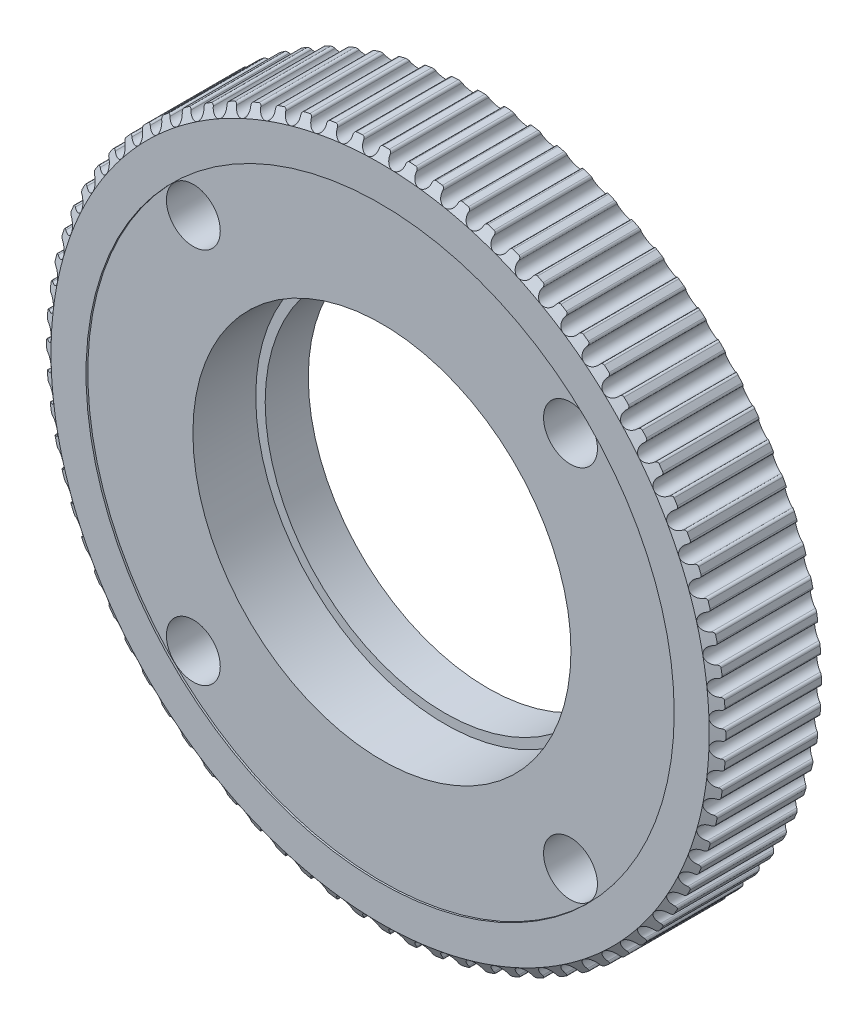
SolidWorks part; units mm, degrees
ref_plane "Front Plane" through (0, 0, 0) normal (0, 0, 1) x (1, 0, 0)
ref_plane "Top Plane" through (0, 0, 0) normal (0, 1, 0) x (1, 0, 0)
ref_plane "Right Plane" through (0, 0, 0) normal (1, 0, 0) x (0, 0, -1)
sketch "Sketch1" plane through (0, 0, 0) normal (0, 0, 1) x (1, 0, 0)
  circle A0 centre (0, 0) radius 37.8162
  circle A1 centre (0, 0) radius 38.1972 construction
  dimension "D1" = 76.3944
  dimension "D2" = 0.381
extrude "Boss-Extrude1" add sketch "Sketch1" along normal mid plane 12
sketch "Sketch2" plane through (0, 0, 6) normal (0, 0, 1) x (1, 0, 0)
  line L0 (0, 0) -> (0, 37.8162) construction
  line L1 (0, 0) -> (1.4847, 37.787) construction
  line L2 (0, 0) -> (-1.4847, 37.787) construction
  line L3 (-1.4387, 36.6179) -> (-1.5286, 38.9064)
  line L4 (1.4387, 36.6179) -> (1.4847, 37.787)
  line L5 (1.4847, 37.787) -> (1.5223, 38.7452)
  line L6 (1.5223, 38.7452) -> (-1.5286, 38.9064)
  circle A0 centre (0, 0) radius 37.8162 construction
  circle A1 centre (0, 0) radius 36.6462 construction
  circle A2 centre (1.4729, 37.4873) radius 0.87 construction
  circle A3 centre (-1.4729, 37.4873) radius 0.87 construction
  circle A4 centre (-0.3449, 37.5546) radius 0.26 construction
  circle A5 centre (0.3449, 37.5546) radius 0.26 construction
  circle A8 centre (0, 0) radius 37.8162
  circle A9 centre (0, 0) radius 37.8162 construction
  arc A10 (0.3473, 37.8146) -> (-0.3473, 37.8146) centre (0, 0) ccw
  arc A11 (0.3473, 37.8146) -> (0.6044, 37.5391) centre (0.3449, 37.5546) cw
  arc A12 (0.6044, 37.5391) -> (1.4387, 36.6179) centre (1.4729, 37.4873) ccw
  arc A13 (-0.3473, 37.8146) -> (-0.6044, 37.5391) centre (-0.3449, 37.5546) ccw
  arc A14 (-0.6044, 37.5391) -> (-1.4387, 36.6179) centre (-1.4729, 37.4873) cw
  dimension "D1" = 1.17
  dimension "D4" = 1.74
  dimension "D5" = 0.52
  dimension "D2" = 2.25
  dimension "D3" = 2.25
  dimension "D6" = 0
extrude "Cut-Extrude1" cut sketch "Sketch2" against normal through all both and the other way through all
pattern_circular "CirPattern1" count 80 over 360 about axis through (0, 0, 6) along (0, 0, -1) of "Cut-Extrude1"
sketch "Sketch3" plane through (0, 0, 6) normal (0, 0, 1) x (1, 0, 0)
  circle A0 centre (0, 0) radius 21.05
  dimension "D1" = 42.1
extrude "Cut-Extrude2" cut sketch "Sketch3" against normal blind 7.2
sketch "Sketch4" plane through (0, 0, -1.2) normal (0, 0, 1) x (1, 0, 0)
  circle A0 centre (0, 0) radius 20
  dimension "D1" = 40
extrude "Cut-Extrude3" cut sketch "Sketch4" against normal through all
sketch "Sketch5" plane through (0, 0, 6) normal (0, 0, 1) x (1, 0, 0)
  circle A0 centre (0, 0) radius 36.6462
  dimension "D1" = 73.2924
extrude "Cut-Extrude4" cut sketch "Sketch5" against normal blind 7 draft 60 flip side to cut
mirror "Mirror1" about plane through (0, 0, 0) normal (0, 0, 1) of "Cut-Extrude4"
sketch "Sketch8" plane through (0, 0, 6) normal (0, 0, 1) x (1, 0, 0)
  circle A0 centre (0, 0) radius 32.75
  dimension "D1" = 65.5
extrude "Cut-Extrude6" cut sketch "Sketch8" against normal blind 0.2
sketch "Sketch9" plane through (0, 0, 5.8) normal (0, 0, 1) x (1, 0, 0)
  line L1 (-21, -21) -> (21, -21) construction
  line L2 (-21, -21) -> (-21, 21) construction
  line L3 (-21, 21) -> (21, 21) construction
  line L4 (21, -21) -> (21, 21) construction
  line L5 (-21, -21) -> (21, 21) construction
  line L6 (-21, 21) -> (21, -21) construction
  line L7 (-37.5, -37.5) -> (37.5, -37.5) construction
  line L8 (-37.5, -37.5) -> (-37.5, 37.5) construction
  line L9 (-37.5, 37.5) -> (37.5, 37.5) construction
  line L10 (37.5, -37.5) -> (37.5, 37.5) construction
  line L11 (-37.5, -37.5) -> (37.5, 37.5) construction
  line L12 (-37.5, 37.5) -> (37.5, -37.5) construction
  circle A0 centre (21, 21) radius 3
  point P0 (0, 0)
  point P7 (0, 0)
  dimension "D2" = 6
  dimension "D1" = 42
  dimension "D3" = 75
extrude "Cut-Extrude7" cut sketch "Sketch9" against normal through all
pattern_circular "CirPattern2" count 4 over 360 about axis through (0, 0, -1.2) along (0, 0, 1) of "Cut-Extrude7"
